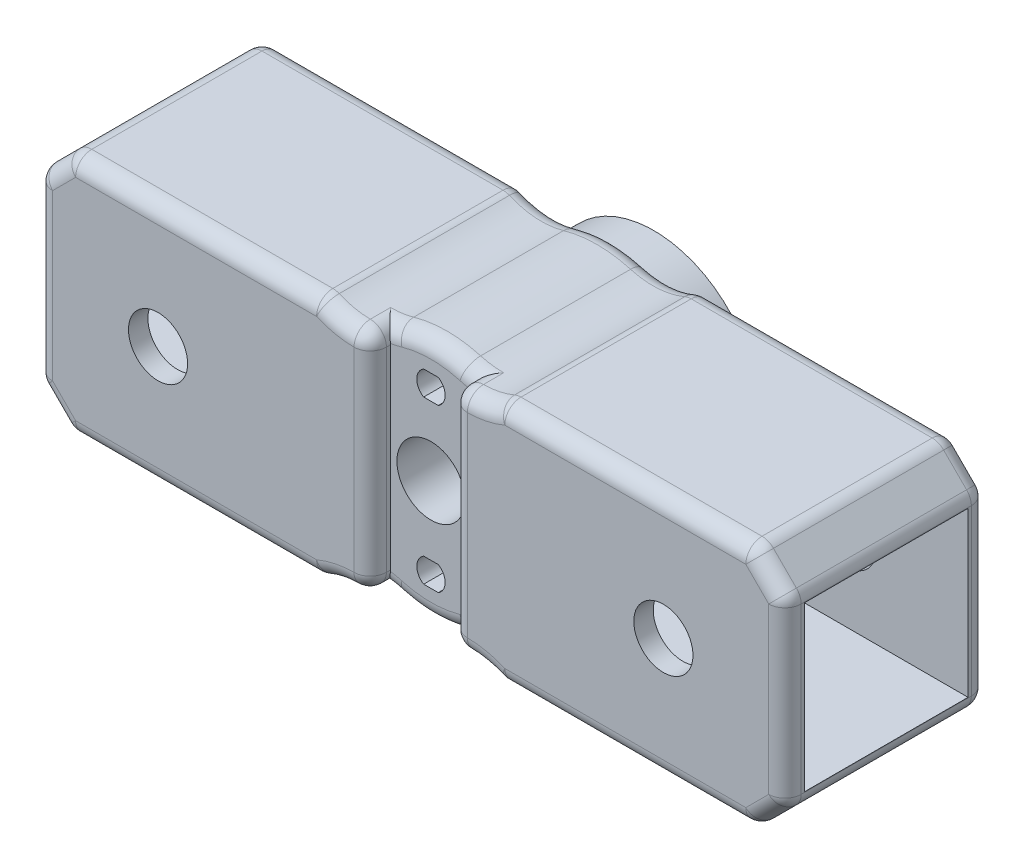
SolidWorks part; units mm, degrees
ref_plane "Alzado" through (0, 0, 0) normal (0, 0, 1) x (1, 0, 0)
ref_plane "Planta" through (0, 0, 0) normal (0, 1, 0) x (1, 0, 0)
ref_plane "Vista lateral" through (0, 0, 0) normal (1, 0, 0) x (0, 0, -1)
sketch "Croquis1" plane through (0, 0, 0) normal (0, 0, 1) x (1, 0, 0)
  circle A0 centre (0, 0) radius 15
  circle A1 centre (0, 0) radius 11.1
  dimension "D1" = 30
  dimension "D2" = 22.2
extrude "Saliente-Extruir1" add sketch "Croquis1" along normal mid plane 25
sketch "Croquis10" plane through (0, 0, 12.5) normal (0, 0, 1) x (1, 0, 0)
  line L0 (11.1803, 0) -> (-11.1803, 0) construction
  line L1 (0, 0) -> (0, 10.6419) construction
  line L2 (-11.1803, -15) -> (-11.1803, 15)
  line L3 (-11.1803, 15) -> (-46.1803, 15)
  line L4 (-46.1803, 15) -> (-46.1803, -15)
  line L5 (-46.1803, -15) -> (-11.1803, -15)
  line L6 (46.1803, 15) -> (46.1803, -15)
  line L7 (11.1803, 15) -> (46.1803, 15)
  line L8 (11.1803, -15) -> (11.1803, 15)
  line L9 (46.1803, -15) -> (11.1803, -15)
  line L10 (-11.1803, 0) -> (-46.1803, 0) construction
  circle A1 centre (-31.1803, 0) radius 3.65
  circle A2 centre (31.1803, 0) radius 3.65
  point P5 (0, 0)
  point P13 (-11.1803, 0)
  dimension "D3" = 7.3
  dimension "D1" = 35
  dimension "D2" = 30
  dimension "D4" = 15
extrude "Saliente-Extruir8" add sketch "Croquis10" against normal blind 25
sketch "Croquis11" plane through (0, 0, -12.5) normal (0, 0, 1) x (1, 0, 0)
  line L6 (0, 0) -> (0, 7.4469) construction
  line L7 (16.1803, -10) -> (36.1803, -10)
  line L8 (16.1803, 10) -> (16.1803, -10)
  line L9 (36.1803, 10) -> (16.1803, 10)
  line L10 (36.1803, -10) -> (36.1803, 10)
  dimension "D1" = 20
extrude "Cortar-Extruir1" [suppressed] cut sketch "Croquis11" along normal blind 10
sketch "Croquis12" plane through (0, 0, 12.5) normal (0, 0, 1) x (1, 0, 0)
  line L0 (-46.1803, 15) -> (-26.1803, 15)
  line L1 (-11.1803, 15) -> (-46.1803, 15) construction
  line L2 (-26.1803, 15) -> (-26.1803, -15)
  line L3 (-46.1803, -15) -> (-11.1803, -15) construction
  line L4 (-26.1803, -15) -> (-46.1803, -15)
  line L5 (-46.1803, -15) -> (-46.1803, 15)
  dimension "D1" = 20
extrude "Cortar-Extruir2" [suppressed] cut sketch "Croquis12" against normal blind 10
sketch "Croquis13" plane through (0, 0, 12.5) normal (0, 0, 1) x (1, 0, 0)
  circle A0 centre (0, 0) radius 11.1
  circle A1 centre (0, 0) radius 4.2
  dimension "D1" = 22.2
  dimension "D2" = 8.4
extrude "Saliente-Extruir9" add sketch "Croquis13" against normal blind 12.8
sketch "Croquis14" plane through (0, 0, -12.5) normal (0, 0, -1) x (-1, 0, 0)
  circle A0 centre (0, 0) radius 11.1
  circle A1 centre (0, 0) radius 13
  dimension "D1" = 22.2
  dimension "D2" = 26
extrude "Saliente-Extruir10" add sketch "Croquis14" along normal blind 5
sketch "Croquis15" plane through (0, 0, 12.5) normal (0, 0, 1) x (1, 0, 0)
  line L0 (-5, 0) -> (-5, 15)
  line L1 (-5, 15) -> (5, 15)
  line L2 (5, 15) -> (5, -15)
  line L3 (5, -15) -> (-5, -15)
  line L4 (-5, -15) -> (-5, 0)
  point P3 (0, 15)
  dimension "D1" = 10
  dimension "D2" = 30
extrude "Cortar-Extruir3" cut sketch "Croquis15" against normal blind 2.5
sketch "Croquis16" plane through (0, 0, 10) normal (0, 0, 1) x (1, 0, 0)
  line L0 (0, 15) -> (0, 10) construction
  line L1 (0, 10) -> (0, 0) construction
  line L2 (0, 0) -> (0, -10) construction
  line L3 (0, -10) -> (0, -15) construction
  line L4 (-0.9014, 11.5) -> (0.9014, 11.5)
  line L5 (-0.9014, 8.5) -> (0.9014, 8.5)
  line L6 (0, 0) -> (-3.0161, 0) construction
  line L7 (-0.9014, -8.5) -> (0.9014, -8.5)
  line L8 (-0.9014, -11.5) -> (0.9014, -11.5)
  arc A0 (5, 14.1421) -> (-5, 14.1421) centre (0, 0) ccw construction
  arc A1 (-5, -14.1421) -> (5, -14.1421) centre (0, 0) ccw construction
  arc A2 (-0.9014, 11.5) -> (-0.9014, 8.5) centre (0, 10) ccw
  arc A3 (0.9014, 8.5) -> (0.9014, 11.5) centre (0, 10) ccw
  arc A4 (-0.9014, -11.5) -> (-0.9014, -8.5) centre (0, -10) cw
  arc A5 (0.9014, -8.5) -> (0.9014, -11.5) centre (0, -10) cw
  point P16 (0, 11.5)
  point P19 (0, 8.5)
  dimension "D2" = 3.5
  dimension "D1" = 5
  dimension "D3" = 3
extrude "Cortar-Extruir4" cut sketch "Croquis16" against normal blind 7.5
sketch "Croquis17" plane through (-46.1803, 0, 0) normal (-1, 0, 0) x (0, 0, 1)
  line L1 (10.1, 10.1) -> (-10.1, 10.1)
  line L2 (10.1, 10.1) -> (10.1, -10.1)
  line L3 (10.1, -10.1) -> (-10.1, -10.1)
  line L4 (-10.1, 10.1) -> (-10.1, -10.1)
  line L5 (10.1, 10.1) -> (-10.1, -10.1) construction
  line L6 (10.1, -10.1) -> (-10.1, 10.1) construction
  point P0 (0, 0)
  dimension "D1" = 20.2
  dimension "D2" = 20.2
extrude "Cortar-Extruir5" cut sketch "Croquis17" against normal blind 30
mirror "Simetría1" about plane through (0, 0, 0) normal (1, 0, 0) of "Cortar-Extruir5"
fillet "Redondeo1" radius 10 4 edges at (-11.1803, 10, 0) (11.1803, 10, 0) (-11.1803, -10, 0) (11.1803, -10, 0)
chamfer "Chaflán1" distance 4 angle 45 4 edges at (46.1803, 15, 0) (46.1803, -15, 0) (-46.1803, 15, 0) (-46.1803, -15, 0)
fillet "Redondeo2" radius 2 54 edges at (-42.1803, -15, 0) (-44.1803, -13, 12.5) (-26.6803, -15, 12.5) (-11.1803, -15, 0) (-26.6803, -15, -12.5) (-46.1803, -11, 0) (-44.1803, -13, -12.5) (-46.1803, 0, 12.5) (-8.1531, -14.1125, 12.5) (-5, -14.2122, 11.25) (-7.7098, -14.066, -12.5) (-46.1803, 0, -12.5) (-46.1803, 11, 0) (-44.1803, 13, 12.5) (-5, 0, 12.5) (-5, 14.2122, 11.25) (-4.5643, -14.3061, 10) (0, -15, -12.5) (-42.1803, 15, 0) (-44.1803, 13, -12.5) (-26.6803, 15, 12.5) (-8.1531, 14.1125, 12.5) (-4.5643, 14.3061, 10) (0, -15, 10) (7.7098, -14.066, -12.5) (-26.6803, 15, -12.5) (-11.1803, 15, 0) (0, 15, 10) (4.5643, -14.3061, 10) (11.1803, -15, 0) (26.6803, -15, -12.5) (-7.7098, 14.066, -12.5) (4.5643, 14.3061, 10) (8.1531, -14.1125, 12.5) (5, -14.2122, 11.25) (26.6803, -15, 12.5) (42.1803, -15, 0) (44.1803, -13, -12.5) (0, 15, -12.5) (5, 14.2122, 11.25) (5, 0, 12.5) (46.1803, -11, 0) (44.1803, -13, 12.5) (46.1803, 0, -12.5) (7.7098, 14.066, -12.5) (8.1531, 14.1125, 12.5) (11.1803, 15, 0) (46.1803, 0, 12.5) (46.1803, 11, 0) (44.1803, 13, -12.5) (26.6803, 15, -12.5) (26.6803, 15, 12.5) (44.1803, 13, 12.5) (42.1803, 15, 0)
